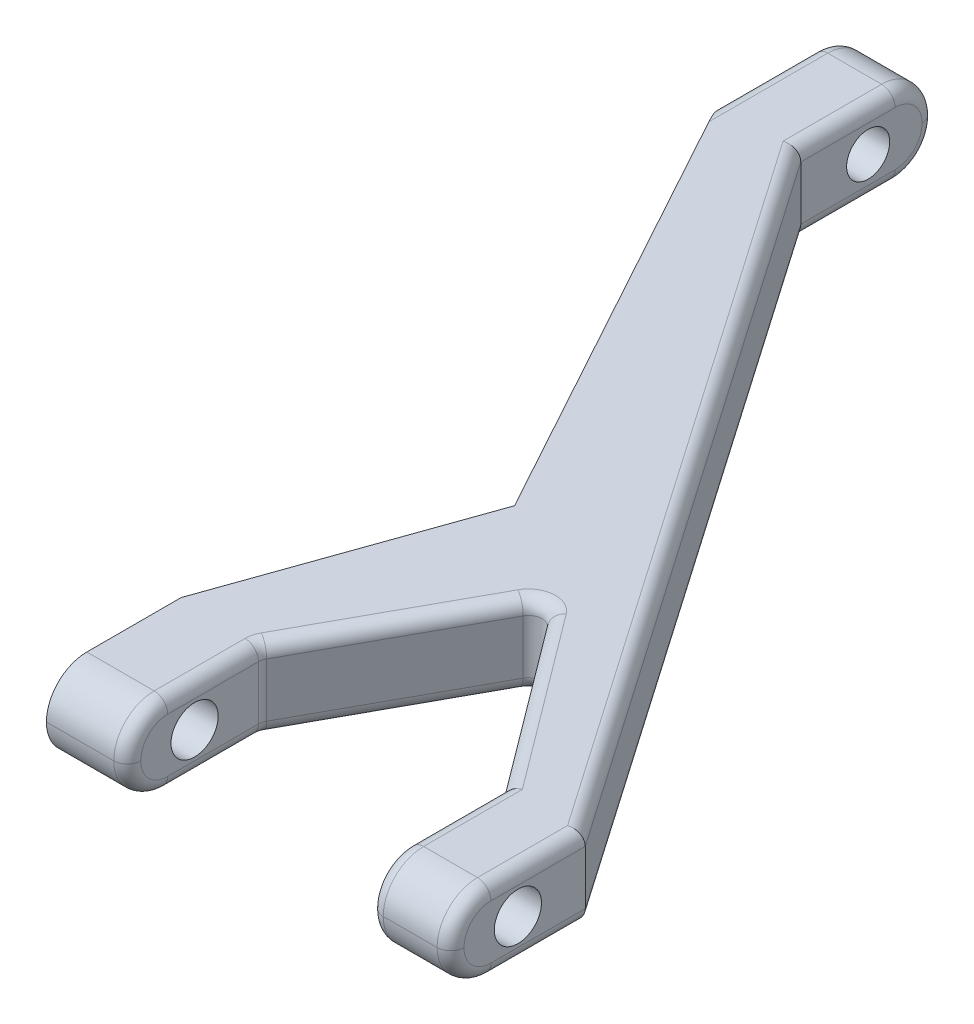
SolidWorks part; units mm, degrees
ref_plane "Front Plane" through (0, 0, 0) normal (0, 0, 1) x (1, 0, 0)
ref_plane "Top Plane" through (0, 0, 0) normal (0, 1, 0) x (1, 0, 0)
ref_plane "Right Plane" through (0, 0, 0) normal (1, 0, 0) x (0, 0, -1)
sketch "Sketch2" plane through (0, 0, 0) normal (0, 1, 0) x (1, 0, 0)
  line L1 (6, -72) -> (12, -72)
  line L2 (12, -72) -> (12, -62)
  line L3 (12, -62) -> (19.626, -48.122)
  line L4 (19.626, -48.122) -> (30, -62)
  line L5 (30, -62) -> (30, -72)
  line L6 (30, -72) -> (36, -72)
  line L7 (36, -72) -> (36, -62)
  line L8 (36, -62) -> (0, -10)
  line L9 (0, -10) -> (0, 0)
  line L10 (0, 0) -> (-6, 0)
  line L11 (-6, 0) -> (-6, -10)
  line L12 (-6, -10) -> (12.4717, -43.7217)
  line L13 (12.4717, -43.7217) -> (6, -62)
  line L14 (6, -62) -> (6, -72)
  point P2 (-3, 0)
  point P14 (9, -72)
  point P15 (33, -72)
  dimension "D1" = 10
  dimension "D2" = 6
  dimension "D3" = 10
  dimension "D4" = 10
  dimension "D5" = 6
  dimension "D6" = 6
  dimension "D8" = 12
  dimension "D9" = 36
  dimension "78" = 72
extrude "Boss-Extrude1" add sketch "Sketch2" along normal blind 6
sketch "Sketch3" plane through (36, 0, 0) normal (1, 0, 0) x (0, 0, -1)
  line L0 (-72, 0) -> (-62, 0) construction
  line L1 (-72, 6) -> (-72, 0) construction
  circle A0 centre (-67, 3) radius 1.75
  dimension "D1" = 3
  dimension "D3" = 3.5
  dimension "D2" = 5
extrude "Cut-Extrude1" cut sketch "Sketch3" against normal through all
sketch "Sketch4" plane through (0, 0, 0) normal (1, 0, 0) x (0, 0, -1)
  line L0 (0, 6) -> (0, 0) construction
  line L1 (-10, 0) -> (0, 0) construction
  circle A0 centre (-5, 3) radius 1.6
  dimension "D1" = 5
  dimension "D3" = 3.2
  dimension "D2" = 3
extrude "Cut-Extrude2" cut sketch "Sketch4" against normal through all
fillet "Fillet1" radius 3 6 edges at (-3, 0, 0) (-3, 6, 0) (33, 0, 72) (33, 6, 72) (9, 0, 72) (9, 6, 72)
fillet "Fillet2" radius 1 28 edges at (12, 5.1213, 71.1213) (12, 0.8787, 71.1213) (12, 6, 65.5) (12, 0, 65.5) (24.813, 6, 55.061) (24.813, 0, 55.061) (36, 0, 65.5) (36, 0.8787, 71.1213) (36, 5.1213, 71.1213) (0, 0, 6.5) (0, 0.8787, 0.8787) (0, 5.1213, 0.8787) (-6, 0.8787, 0.8787) (-6, 5.1213, 0.8787) (12, 3, 62) (15.813, 6, 55.061) (19.626, 3, 48.122) (15.813, 0, 55.061) (36, 6, 65.5) (0, 6, 6.5) (-6, 6, 6.5) (-6, 0, 6.5) (18, 0, 36) (18, 6, 36) (30, 0, 65.5) (30, 0.8787, 71.1213) (30, 5.1213, 71.1213) (30, 6, 65.5)
